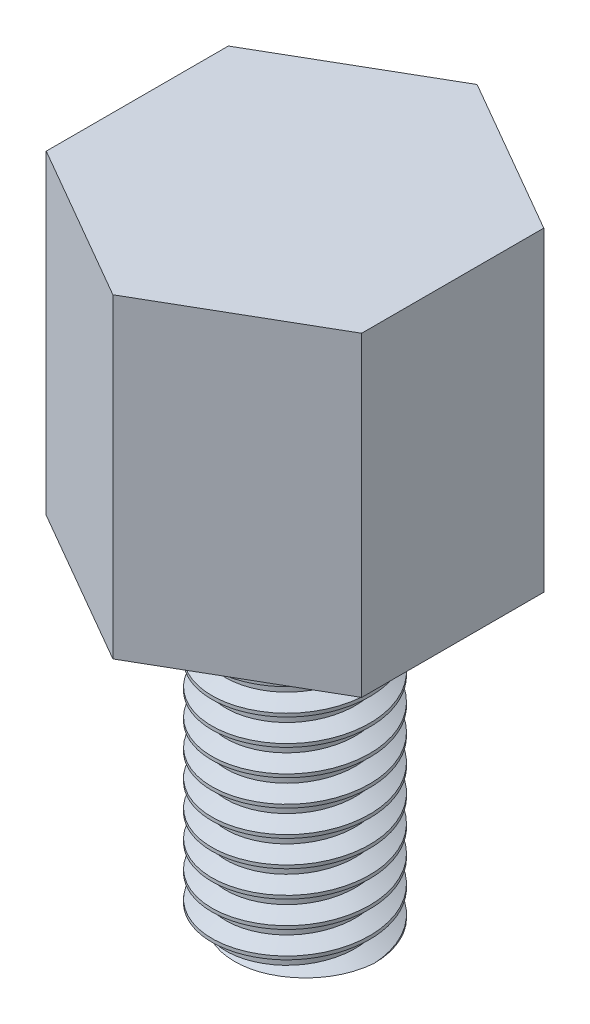
SolidWorks part; units mm, degrees
material "Brass"
ref_plane "Front Plane" through (0, 0, 0) normal (0, 0, 1) x (1, 0, 0)
ref_plane "Top Plane" through (0, 0, 0) normal (0, 1, 0) x (1, 0, 0)
ref_plane "Right Plane" through (0, 0, 0) normal (1, 0, 0) x (0, 0, -1)
sketch "Sketch1" plane through (0, 0, 0) normal (0, 1, 0) x (1, 0, 0)
  line L1 (3, 1.7321) -> (0, 3.4641)
  line L2 (0, 3.4641) -> (-3, 1.7321)
  line L3 (-3, 1.7321) -> (-3, -1.7321)
  line L4 (-3, -1.7321) -> (0, -3.4641)
  line L5 (0, -3.4641) -> (3, -1.7321)
  line L6 (3, -1.7321) -> (3, 1.7321)
  circle A0 centre (0, 0) radius 3 construction
  dimension "D1" = 6
extrude "Boss-Extrude1" add sketch "Sketch1" along normal blind 25 contours L2 L3 L4 L5 L6 L1
sketch "Sketch2" plane through (0, 0, 0) normal (0, -1, 0) x (1, 0, 0)
  circle A0 centre (0, 0) radius 1.5
  dimension "D1" = 3
extrude "Boss-Extrude2" add sketch "Sketch2" along normal blind 6
hole_wizard "Tap Drill for M3 Tap1" positions "Sketch3" profile "Sketch4" hole size "M3" standard "ISO"
sketch "Sketch3" plane through (0, 25, 0) normal (0, 1, 0) x (1, 0, 0)
  point P0 (0, 0)
sketch "Sketch4" plane through (0, 25, 0) normal (1, 0, 0) x (0, 0, 1)
  line L0 (0, 0) -> (0, 10.7511)
  line L1 (0, 10.7511) -> (1.25, 10)
  line L2 (1.25, 10) -> (1.25, 0)
  line L5 (1.25, 0) -> (0, 0)
  line L10 (0, 10.7511) -> (-1.25, 10) construction
  line L11 (0, -6.35) -> (0, 107.95) construction
  dimension "Hole Dia." = 2.5
  dimension "Hole Depth" = 10
  dimension "Drill Angle" = 118
thread "Thread1" pitch 0.5 method cut trim with start face yes profile "Thread Profile1" start angle 0, offset 1, length 9, pitch 0.5, diameter 2.5
ref_plane "Plane1" through (-1.25, 26, 0) normal (0, 0, 1) x (-1, 0, 0)
sketch "Thread Profile1" plane through (-1.25, 26, 0) normal (0, 0, 1) x (-1, 0, 0)
  line L0 (0, 0) -> (0, 0.5) construction
  line L1 (0, 0) -> (0.2706, 0.1562)
  line L2 (0.2706, 0.1562) -> (0.2706, 0.2187)
  line L3 (0.2706, 0.2187) -> (0, 0.375)
  line L4 (0.2706, 0.1875) -> (0, 0.1875) construction
  line L11 (0, 0) -> (0, 0.375)
  point P2 (0, 0)
  dimension "Pitch" = 0.5
  dimension "Profile_Angle" = 60
  dimension "Profile_Land" = 0.0625
  dimension "Profile_Height" = 0.2706
thread "Thread2" pitch 0.5 method cut profile "Thread Profile2" start angle 0, offset 1, length 6.5, pitch 0.5, diameter 3
ref_plane "Plane2" through (1.5, -7, 0) normal (0, 0, 1) x (1, 0, 0)
sketch "Thread Profile2" plane through (1.5, -7, 0) normal (0, 0, 1) x (1, 0, 0)
  line L0 (0, 0) -> (0, 0.5) construction
  line L11 (0, 0) -> (0, 0.4375)
  line L12 (0, 0.4375) -> (-0.2706, 0.2812)
  line L13 (-0.2706, 0.2812) -> (-0.2706, 0.1562)
  line L15 (-0.2706, 0.1562) -> (0, 0)
  line L17 (-0.2706, 0.2187) -> (0, 0.2187) construction
  point P2 (0, 0)
  dimension "Pitch" = 0.5
  dimension "Profile_Angle" = 60
  dimension "Profile_Land" = 0.125
  dimension "Profile_Height" = 0.2706
sketch "Sketch9" plane through (0, 0, 0) normal (0, 1, 0) x (1, 0, 0)
  circle A0 centre (0, 0) radius 1.225
  dimension "D1" = 2.45
extrude "Cut-Extrude-Thin1" cut sketch "Sketch9" against normal blind 0.5 thin contours A0 thin type one direction wall 10
ref_plane "基准面1" through (0, 6, 0) normal (0, -1, 0) x (-1, 0, 0)
sketch "草图1" plane through (0, 6, 0) normal (0, -1, 0) x (-1, 0, 0)
  line L1 (5.3632, 6.5065) -> (-7.2159, 6.5065)
  line L2 (5.3632, 6.5065) -> (5.3632, -6.6151)
  line L3 (5.3632, -6.6151) -> (-7.2159, -6.6151)
  line L4 (-7.2159, 6.5065) -> (-7.2159, -6.6151)
extrude "切除-拉伸1" cut sketch "草图1" against normal blind 27
